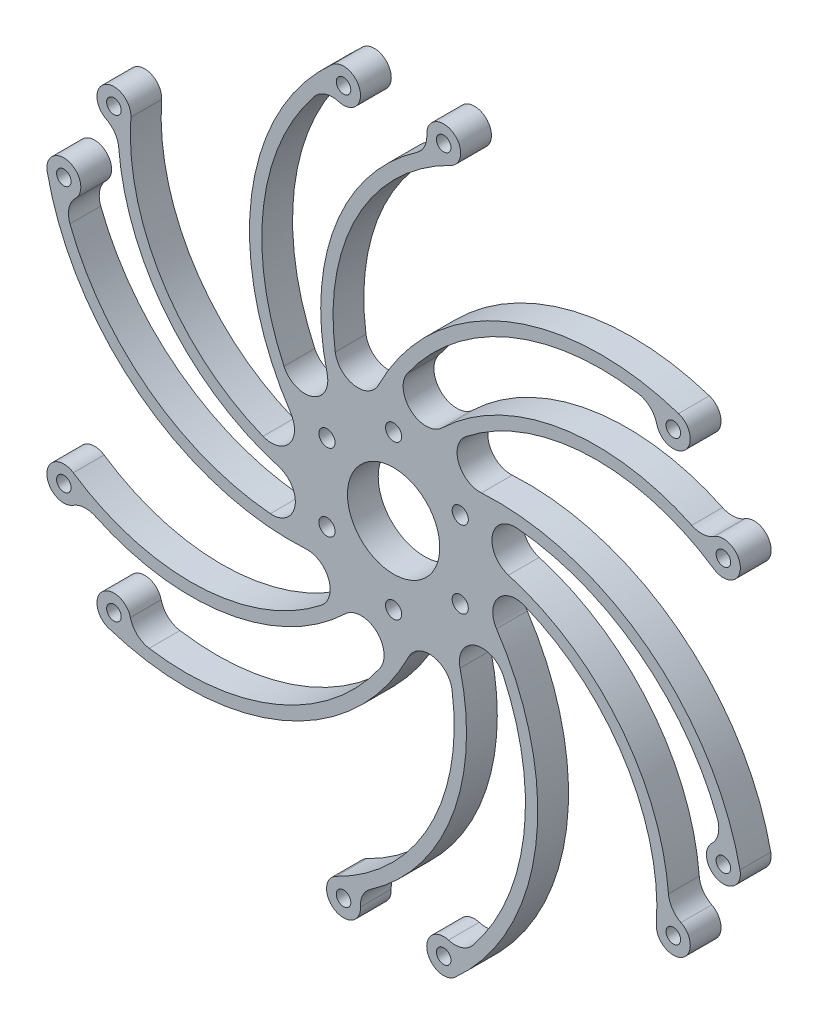
SolidWorks part; units mm, degrees
ref_plane "Front Plane" through (0, 0, 0) normal (0, 0, 1) x (1, 0, 0)
ref_plane "Top Plane" through (0, 0, 0) normal (0, 1, 0) x (1, 0, 0)
ref_plane "Right Plane" through (0, 0, 0) normal (1, 0, 0) x (0, 0, -1)
sketch "Sketch1" plane through (0, 0, 0) normal (0, 0, 1) x (1, 0, 0)
  line L0 (0, 0) -> (0, 108.9025) construction
  line L1 (15.5, 108.9025) -> (-15.5, 108.9025) construction
  line L2 (0, 0) -> (-20.6222, 11.9062) construction
  line L7 (-30.8724, 7.4134) -> (-79.06, 120.9362) construction
  line L9 (0, 0) -> (-9.016, 30.443) construction
  line L10 (-30.8724, 7.4134) -> (0, 0) construction
  line L11 (-27.4796, 27.4796) -> (0, 0) construction
  circle A0 centre (0, 0) radius 110 construction
  circle A1 centre (-15.5, 108.9025) radius 5.25
  circle A2 centre (15.5, 108.9025) radius 5.25
  circle A3 centre (-15.5, 108.9025) radius 2.25
  circle A4 centre (15.5, 108.9025) radius 2.25
  circle A5 centre (0, 0) radius 23.8125 construction
  circle A6 centre (0, 0) radius 31.75
  circle A7 centre (-20.6222, 11.9062) radius 2.5
  arc A8 (-19.0049, 112.8112) -> (-31.8536, 12.9939) centre (32.4256, 55.4553) ccw
  arc A9 (-16.976, 103.8642) -> (-24.5046, 101.5122) centre (-18.9754, 97.0391) ccw
  circle A10 centre (0, 0) radius 14.2875
  arc A12 (10.2578, 108.6168) -> (7.1998, 102.3792) centre (3.1563, 108.2299) cw
  arc A13 (17.8051, 104.1856) -> (-18.0734, 36.2373) centre (46.4211, 45.629) ccw
  arc A14 (7.1998, 102.3792) -> (-20.5728, 29.1758) centre (46.4211, 45.629) ccw
  arc A15 (-24.5046, 101.5122) -> (-33.9235, 24.4703) centre (32.4256, 55.4553) ccw
  arc A16 (-18.0734, 36.2373) -> (-9.016, 30.443) centre (-11.0356, 37.2622) ccw
  arc A17 (-33.9235, 24.4703) -> (-20.5728, 29.1758) centre (-27.4796, 27.4796) ccw
  arc A18 (-31.8536, 12.9939) -> (-30.8724, 7.4134) centre (-37.7878, 9.0739) cw
  point P15 (-79.2719, 120.7577)
  dimension "D1" = 220
  dimension "D3" = 4.5
  dimension "D6" = 47.625
  dimension "D7" = 5
  dimension "D8" = 7.112
  dimension "D9" = 28.575
  dimension "D13" = 63.5
  dimension "D2" = 31
  dimension "D4" = 3
  dimension "D5" = 60
  dimension "D11" = 3.81
  dimension "D12" = 3.81
  dimension "D14" = 60
  dimension "D10" = 45
  dimension "D15" = 23
extrude "Boss-Extrude1" add sketch "Sketch1" along normal mid plane 9.525 contours A6 A10 | A7 region at (-26.9179, 15.0756, 0)
extrude "Boss-Extrude2" add sketch "Sketch1<3>" along normal up to surface and the other way up to surface contours A17 A6 A13 A2 A12 A14 | A17 A15 A9 A1 A8 A6 | A16 A13 A6 | A1 A3 | A2 A4 region at (-12.4415, 104.8195, 0) region at (-21.6826, 107.5004, 0) region at (-19.7131, 25.311, 0) region at (12.917, 104.5032, 0) up to face at (14.2875, 0, 4.7625) other way up to face at (14.2875, 0, -4.7625)
sketch "Sketch1<3>" plane through (0, 0, 0) normal (0, 0, 1) x (1, 0, 0) same geometry as "Sketch1"
extrude "Cut-Extrude1" cut sketch "Sketch1<5>" against normal through all both and the other way through all contours A7 region at (-20.6222, 11.9062, 0)
sketch "Sketch1<5>" plane through (0, 0, 0) normal (0, 0, 1) x (1, 0, 0) same geometry as "Sketch1"
pattern_circular "CirPattern1" count 6 over 360 about axis through (0, 0, 4.7625) along (0, 0, -1) of "Boss-Extrude2", "Cut-Extrude1" reverse direction yes
equation "\"D12@Sketch1\"=\"D11@Sketch1\""
